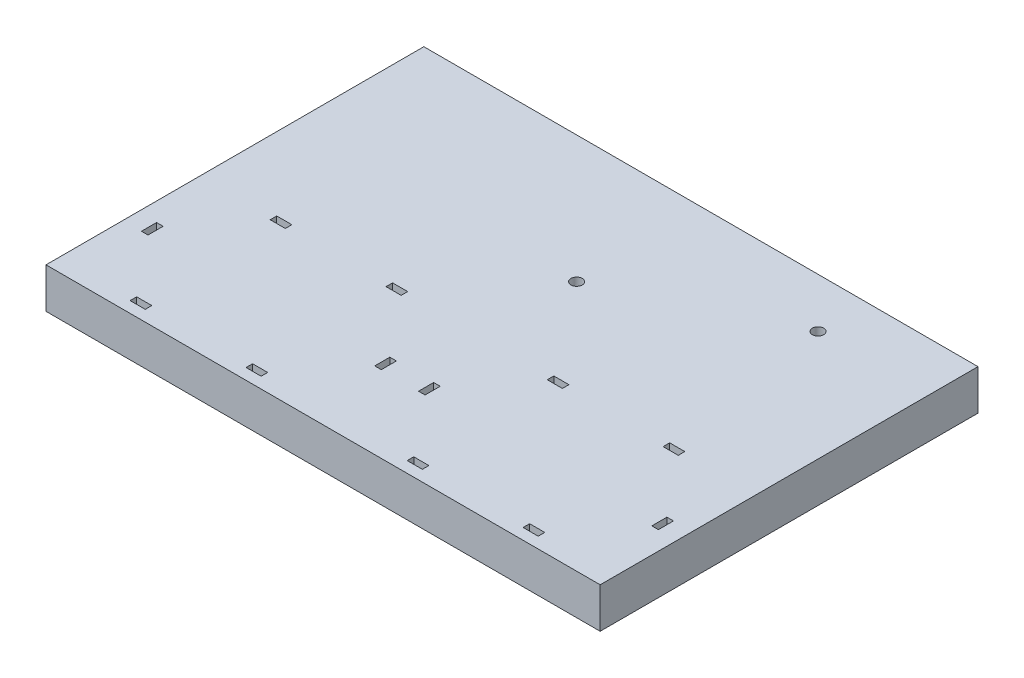
SolidWorks part; units mm, degrees
ref_plane "Front Plane" through (0, 0, 0) normal (0, 0, 1) x (1, 0, 0)
ref_plane "Top Plane" through (0, 0, 0) normal (0, 1, 0) x (1, 0, 0)
ref_plane "Right Plane" through (0, 0, 0) normal (1, 0, 0) x (0, 0, -1)
sketch "Sketch1" plane through (0, 0, 0) normal (0, 1, 0) x (1, 0, 0)
  line L0 (-66.0627, 0) -> (65.2437, 0) construction
  line L1 (-55, 37.5) -> (55, 37.5)
  line L2 (-55, 37.5) -> (-55, -37.5)
  line L3 (-55, -37.5) -> (55, -37.5)
  line L4 (55, 37.5) -> (55, -37.5)
  line L5 (27.5, -7.5) -> (27.5, -34) construction
  line L6 (5, -7.5) -> (50, -7.5) construction
  line L7 (5, -7.5) -> (5, -34) construction
  line L8 (5, -34) -> (50, -34) construction
  line L9 (50, -7.5) -> (50, -34) construction
  line L10 (-10.21, 30.09) -> (35, 30.09) construction
  line L11 (-10.21, 30.09) -> (-10.21, 10) construction
  line L12 (-10.21, 10) -> (35, 10) construction
  line L13 (35, 30.09) -> (35, 10) construction
  line L14 (-10.21, 30.09) -> (35, 10) construction
  line L15 (-10.21, 10) -> (35, 30.09) construction
  line L16 (5, -20.75) -> (50, -20.75) construction
  line L17 (14.5, -35.3) -> (17.5, -35.3)
  line L18 (14.5, -7.5) -> (17.5, -7.5)
  line L19 (14.5, -7.5) -> (14.5, -6.2)
  line L20 (14.5, -6.2) -> (17.5, -6.2)
  line L21 (17.5, -7.5) -> (17.5, -6.2)
  line L22 (17.5, -34) -> (17.5, -35.3)
  line L23 (14.5, -34) -> (17.5, -34)
  line L24 (14.5, -34) -> (14.5, -35.3)
  line L25 (40.5, -7.5) -> (40.5, -6.2)
  line L26 (40.5, -6.2) -> (37.5, -6.2)
  line L27 (40.5, -7.5) -> (37.5, -7.5)
  line L28 (37.5, -7.5) -> (37.5, -6.2)
  line L29 (40.5, -34) -> (40.5, -35.3)
  line L30 (37.5, -34) -> (37.5, -35.3)
  line L31 (40.5, -34) -> (37.5, -34)
  line L32 (40.5, -35.3) -> (37.5, -35.3)
  line L33 (51.3, -22.25) -> (50, -22.25)
  line L34 (3.7, -19.25) -> (5, -19.25)
  line L35 (3.7, -19.25) -> (3.7, -22.25)
  line L36 (3.7, -22.25) -> (5, -22.25)
  line L37 (5, -19.25) -> (5, -22.25)
  line L38 (51.3, -19.25) -> (50, -19.25)
  line L39 (51.3, -19.25) -> (51.3, -22.25)
  line L40 (50, -19.25) -> (50, -22.25)
  line L41 (0, -62.4684) -> (0, 56.3378) construction
  line L48 (-50, -19.25) -> (-50, -22.25)
  line L49 (-51.3, -19.25) -> (-51.3, -22.25)
  line L50 (-51.3, -19.25) -> (-50, -19.25)
  line L51 (-5, -19.25) -> (-5, -22.25)
  line L52 (-3.7, -22.25) -> (-5, -22.25)
  line L53 (-3.7, -19.25) -> (-3.7, -22.25)
  line L54 (-3.7, -19.25) -> (-5, -19.25)
  line L55 (-51.3, -22.25) -> (-50, -22.25)
  line L56 (-40.5, -35.3) -> (-37.5, -35.3)
  line L57 (-40.5, -34) -> (-37.5, -34)
  line L58 (-37.5, -34) -> (-37.5, -35.3)
  line L59 (-40.5, -34) -> (-40.5, -35.3)
  line L60 (-37.5, -7.5) -> (-37.5, -6.2)
  line L61 (-40.5, -7.5) -> (-37.5, -7.5)
  line L62 (-40.5, -6.2) -> (-37.5, -6.2)
  line L63 (-40.5, -7.5) -> (-40.5, -6.2)
  line L64 (-14.5, -34) -> (-14.5, -35.3)
  line L65 (-14.5, -34) -> (-17.5, -34)
  line L66 (-17.5, -34) -> (-17.5, -35.3)
  line L67 (-17.5, -7.5) -> (-17.5, -6.2)
  line L68 (-14.5, -6.2) -> (-17.5, -6.2)
  line L69 (-14.5, -7.5) -> (-14.5, -6.2)
  line L70 (-14.5, -7.5) -> (-17.5, -7.5)
  line L71 (-14.5, -35.3) -> (-17.5, -35.3)
  circle A2 centre (33.07, 27.68) radius 1.13
  circle A3 centre (0.56, 12.26) radius 1.13
  point P4 (55, 0)
  point P6 (0, 37.5)
  point P23 (12.395, 20.045)
  point P46 (5, -20.75)
  point P53 (0, -37.5)
  dimension "D5" = 5
  dimension "D17" = 2.26
  dimension "D18" = 2.26
  dimension "D1" = 110
  dimension "D2" = 75
  dimension "D3" = 26.5
  dimension "D4" = 45
  dimension "D6" = 7.5
  dimension "D7" = 20
  dimension "D8" = 1.3
  dimension "D9" = 3
  dimension "D13" = 45.21
  dimension "D14" = 20.09
  dimension "D15" = 10
  dimension "D16" = 20
  dimension "D19" = 15.42
  dimension "D20" = 17.68
  dimension "D21" = 32.51
  dimension "D22" = 1.93
extrude "Boss-Extrude1" add sketch "Sketch1" along normal blind 8
